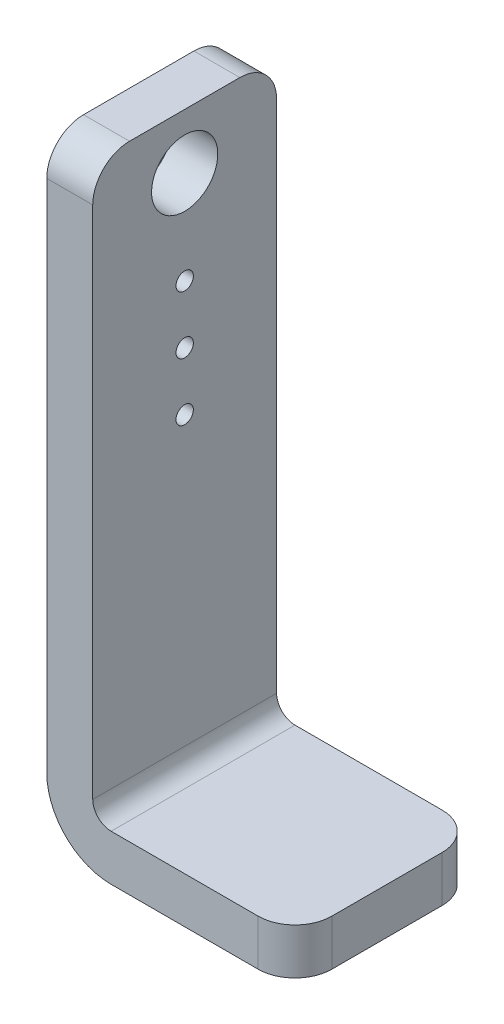
SolidWorks part; units mm, degrees
material "1060 Alloy"
ref_plane "Front Plane" through (0, 0, 0) normal (0, 0, 1) x (1, 0, 0)
ref_plane "Top Plane" through (0, 0, 0) normal (0, 1, 0) x (1, 0, 0)
ref_plane "Right Plane" through (0, 0, 0) normal (1, 0, 0) x (0, 0, -1)
sketch "Sketch1" plane through (0, 0, 0) normal (0, 0, 1) x (1, 0, 0)
  line L0 (0, 26.3645) -> (0, -11.7355)
  line L1 (1.27, -13.0055) -> (13.97, -13.0055)
  line L2 (-3.175, 26.3645) -> (-3.175, -11.7355)
  line L3 (1.27, -16.1805) -> (13.97, -16.1805)
  line L4 (0, 26.3645) -> (-3.175, 26.3645)
  line L5 (13.97, -13.0055) -> (13.97, -16.1805)
  arc A0 (1.27, -13.0055) -> (0, -11.7355) centre (1.27, -11.7355) cw
  arc A1 (1.27, -16.1805) -> (-3.175, -11.7355) centre (1.27, -11.7355) cw
  dimension "D1" = 1.27
  dimension "D3" = 12.7
  dimension "D4" = 38.1
  dimension "D2" = 3.175
extrude "Boss-Extrude1" add sketch "Sketch1" along normal blind 12.7
sketch "Sketch2" plane through (-3.175, 0, 0) normal (-1, 0, 0) x (0, 0, 1)
  line L0 (12.7, 26.3645) -> (0, 26.3645) construction
  line L1 (12.7, 26.3645) -> (0, 26.3645) construction
  line L6 (3.7, 20.3455) -> (4.353, 8.3954)
  line L7 (9, 20.3455) -> (8.347, 8.3954)
  circle A0 centre (6.35, 22.5545) radius 2.286
  arc A6 (9, 20.3455) -> (3.7, 20.3455) centre (6.35, 22.5545) ccw
  arc A7 (4.353, 8.3954) -> (8.347, 8.3954) centre (6.35, 8.5045) ccw
  circle A11 centre (6.35, 8.1045) radius 0.6
  circle A15 centre (6.35, 12.1045) radius 0.6
  circle A17 centre (6.35, 16.1045) radius 0.6
  point P13 (6.35, 26.3645)
  dimension "D1" = 6.9
  dimension "D2" = 4
  dimension "D7" = 1.2
  dimension "D8" = 6.45
  dimension "D10" = 4.572
  dimension "D3" = 11.95
  dimension "D4" = 0.653
  dimension "D5" = 5.3
  dimension "D6" = 3.994
  dimension "D9" = 4
  dimension "D11" = 4
  dimension "D12" = 3.81
extrude "Cut-Extrude1" cut sketch "Sketch2" against normal up to next from surface contours A0 | A17 | A15 | A11 starting at face at (-3.175, 7.3145, 6.35)
sketch "Sketch3" plane through (-3.175, 0, 0) normal (-1, 0, 0) x (0, 0, 1)
  line L0 (6.35, 26.3645) -> (6.35, -11.7355)
  line L1 (12.7, 26.3645) -> (0, 26.3645) construction
  line L2 (12.7, -11.7355) -> (0, -11.7355) construction
fillet "Fillet1" radius 2.54 4 edges at (13.97, -14.593, 0) (13.97, -14.593, 12.7) (-1.5875, 26.3645, 0) (-1.5875, 26.3645, 12.7)
